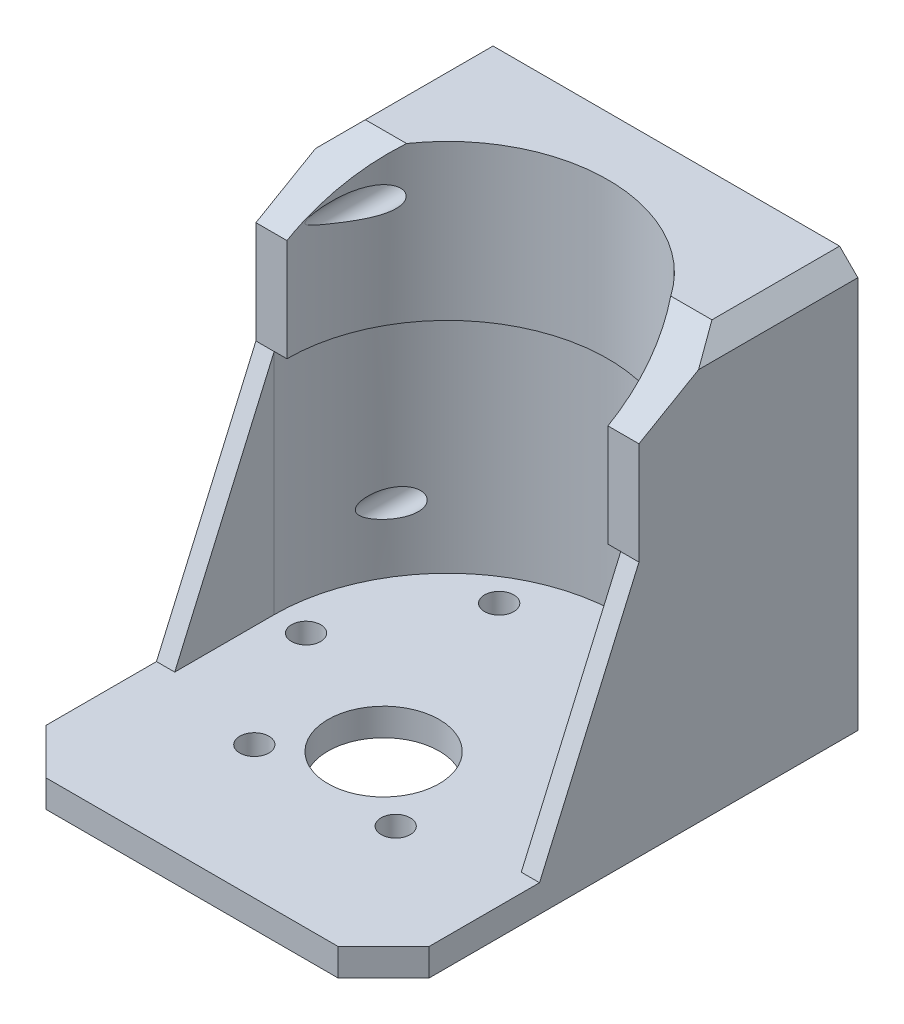
SolidWorks part; units mm, degrees
ref_plane "前视基准面" through (0, 0, 0) normal (0, 0, 1) x (1, 0, 0)
ref_plane "上视基准面" through (0, 0, 0) normal (0, 1, 0) x (1, 0, 0)
ref_plane "右视基准面" through (0, 0, 0) normal (1, 0, 0) x (0, 0, -1)
other "Configuration Table"
sketch "草图2" plane through (0, 0, 255.3138) normal (0, 0, -1) x (-1, 0, 0)
  line L1 (-40.2126, 0) -> (63.1066, 0) construction
  line L12 (21, 18) -> (19, 20)
  line L13 (19, 20) -> (-19, 20)
  line L14 (-19, 20) -> (-21, 18)
  line L15 (-21, 18) -> (-21, -25)
  line L16 (-21, -25) -> (21, -25)
  line L17 (21, -25) -> (21, 18)
  circle A4 centre (16, -15) radius 1.5
  circle A5 centre (16, 15) radius 1.5
  circle A6 centre (-16, 15) radius 1.5
  circle A7 centre (-16, -15) radius 1.5
  point P4 (0, 0)
  point P8 (-16, -15)
  dimension "D2" = 3
  dimension "D1" = 42
  dimension "D3" = 43
  dimension "D4" = 2
  dimension "D5" = 2
  dimension "D6" = 30
  dimension "D7" = 5
  dimension "D8" = 5
  dimension "D9" = 135
  dimension "D10" = 5
extrude "凸台-拉伸1" add sketch "草图2" against normal blind 52
sketch "草图3" plane through (0, -25, 0) normal (0, -1, 0) x (1, 0, 0)
  line L2 (21, 255.3138) -> (-21, 255.3138) construction
  line L3 (21, 307.3138) -> (21, 255.3138) construction
  circle A7 centre (0, 279.3138) radius 19
  circle A8 centre (7.75, 265.8904) radius 1.6
  circle A9 centre (-7.75, 265.8904) radius 1.6
  circle A10 centre (-15.5, 279.3138) radius 1.6
  circle A11 centre (-7.75, 292.7372) radius 1.6
  circle A12 centre (7.75, 292.7372) radius 1.6
  circle A13 centre (15.5, 279.3138) radius 1.6
  point P5 (0, 255.3138)
  point P11 (0, 0)
  dimension "D1" = 3.2
  dimension "D2" = 38
  dimension "D3" = 7.75
  dimension "D4" = 15.5
  dimension "D5" = 7.75
  dimension "D6" = 15.5
  dimension "D7" = 13.4234
  dimension "D8" = 13.4234
  dimension "D9" = 24
  dimension "D10" = 21
extrude "切除-拉伸1" cut sketch "草图3" against normal blind 25 from offset 3 contours A7 A13 A12 A11 A10 A9 A8 | A12 | A11 | A10 | A9 | A8 | A13 | A7 region at (0, -25, 279.3138) region at (7.75, -25, 265.8904) region at (-7.75, -25, 265.8904) region at (-15.5, -25, 279.3138) region at (-7.75, -25, 292.7372) region at (7.75, -25, 292.7372) region at (15.5, -25, 279.3138) offset against normal yes
extrude "切除-拉伸2" cut sketch "草图3<3>" against normal blind 25 contours A11 | A12 | A10 | A9 | A8 | A13 region at (7.75, -25, 265.8904) region at (-7.75, -25, 265.8904) region at (-15.5, -25, 279.3138) region at (-7.75, -25, 292.7372) region at (7.75, -25, 292.7372) region at (15.5, -25, 279.3138)
sketch "草图3<3>" plane through (0, -25, 0) normal (0, -1, 0) x (1, 0, 0) same geometry as "草图3"
sketch "草图5" plane through (0, 3, 0) normal (0, -1, 0) x (1, 0, 0)
  line L0 (21, 255.3138) -> (-21, 255.3138) construction
  line L1 (21, 307.3138) -> (21, 255.3138) construction
  circle A1 centre (0, 279.3138) radius 17.6
  point P1 (0, 0)
  dimension "D1" = 35.2
  dimension "D2" = 24
  dimension "D3" = 21
extrude "切除-拉伸3" cut sketch "草图5" against normal through all contours A1
sketch "草图6" plane through (0, -25, 0) normal (0, -1, 0) x (1, 0, 0)
  circle A2 centre (0, 286.3138) radius 6.1
  dimension "D2" = 21
  dimension "D1" = 12.2
  dimension "D3" = 31
extrude "切除-拉伸4" cut sketch "草图6" against normal up to vertex (43 mm away) up to point (21, 18, 307.3138)
sketch "草图7" plane through (0, 20, 0) normal (0, 1, 0) x (1, 0, 0)
  line L0 (21, -255.3138) -> (21, -307.3138)
  line L1 (21, -255.3138) -> (21, -307.3138) construction
  line L2 (21, -307.3138) -> (-21, -307.3138)
  line L3 (21, -307.3138) -> (-21, -307.3138) construction
  line L4 (-21, -307.3138) -> (-21, -255.3138)
  line L5 (-21, -307.3138) -> (-21, -255.3138) construction
  line L6 (-21, -255.3138) -> (21, -255.3138)
  line L7 (-21, -255.3138) -> (21, -255.3138) construction
  line L8 (21, -279.3138) -> (21, -307.3138)
  line L10 (21, -307.3138) -> (-21, -307.3138)
  line L11 (-21, -307.3138) -> (-21, -279.3138)
  line L12 (-21, -279.3138) -> (21, -279.3138)
  circle A0 centre (0, -286.3138) radius 6.1
  circle A1 centre (0, -286.3138) radius 6.1 construction
  circle A2 centre (-7.75, -292.7372) radius 1.6
  circle A3 centre (-7.75, -292.7372) radius 1.6 construction
  circle A4 centre (7.75, -292.7372) radius 1.6
  circle A5 centre (7.75, -292.7372) radius 1.6 construction
  circle A6 centre (-15.5, -279.3138) radius 1.6
  circle A7 centre (-15.5, -279.3138) radius 1.6 construction
  circle A8 centre (-7.75, -265.8904) radius 1.6
  circle A9 centre (-7.75, -265.8904) radius 1.6 construction
  circle A10 centre (7.75, -265.8904) radius 1.6
  circle A11 centre (7.75, -265.8904) radius 1.6 construction
  circle A12 centre (15.5, -279.3138) radius 1.6
  circle A13 centre (15.5, -279.3138) radius 1.6 construction
extrude "切除-拉伸5" cut sketch "草图7" against normal up to surface (42 mm away) up to face at (0, -22, 280.2138)
chamfer "倒角1" distance 5 angle 45 2 edges at (21, -23.5, 307.3138) (-21, -23.5, 307.3138)
chamfer "倒角5" distance 10 angle 30 2 edges at (-18.3, 20, 279.3138) (18.3, 20, 279.3138) first distance on face at (0, 20, 268.3805)
sketch "草图8" plane through (21, 0, 0) normal (1, 0, 0) x (0, 0, -1)
  line L0 (-279.3138, -22) -> (-279.3138, 2.99)
  line L2 (-279.3138, 2.99) -> (-290.2169, -22)
  line L3 (-302.3138, -22) -> (-279.3138, -22) construction
  line L4 (-290.2169, -22) -> (-279.3138, -22)
  line L5 (-279.3138, -22) -> (-279.3138, 14.2265) construction
  point P3 (-279.3138, 3.1802)
  point P4 (-279.3138, 2.99)
  point P5 (-279.3138, -3.8868)
extrude "凸台-拉伸2" add sketch "草图8" against normal blind 2
mirror "镜向1" about plane through (0, 0, 0) normal (1, 0, 0) of "凸台-拉伸2"
